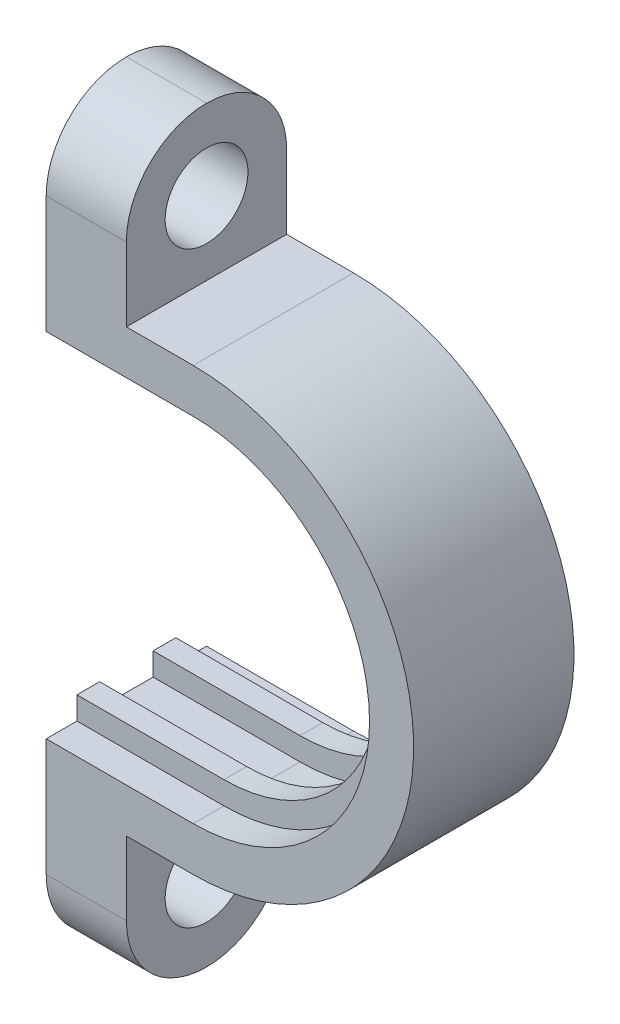
SolidWorks part; units mm, degrees
ref_plane "前视基准面" through (0, 0, 0) normal (0, 0, 1) x (1, 0, 0)
ref_plane "上视基准面" through (0, 0, 0) normal (0, 1, 0) x (1, 0, 0)
ref_plane "右视基准面" through (0, 0, 0) normal (1, 0, 0) x (0, 0, -1)
other "Configuration Table"
sketch "草图1" plane through (0, 0, 0) normal (0, 0, 1) x (1, 0, 0)
  line L14 (-5.5, 14) -> (-5.5, 5.75)
  line L15 (-5.5, -5.75) -> (-5.5, -14)
  line L16 (-2.5, 14) -> (-2.5, 8.25)
  line L17 (-2.5, -8.25) -> (-2.5, -14)
  line L18 (-2.5, 14) -> (-2.5, 8.3853) construction
  line L19 (-2.5, 14) -> (-5.5, 14)
  line L21 (-2.5, -14) -> (-5.5, -14)
  line L22 (-5.5, -1.6771) -> (-5.5, -8.3853) construction
  line L25 (-2.5, -8.3853) -> (-2.5, -8.3853) construction
  line L26 (-2.5, 8.25) -> (0, 8.25)
  line L27 (-2.5, -8.25) -> (0, -8.25)
  line L28 (0, 0) -> (5.75, 0) construction
  line L29 (0, 5.75) -> (-5.5, 5.75)
  line L30 (0, -5.75) -> (-5.5, -5.75)
  line L31 (-5.5, 14) -> (-5.5, 1.6771) construction
  arc A6 (0, 5.75) -> (0, -5.75) centre (0, 0) cw
  arc A8 (-2.5, 8.3853) -> (-2.5, -8.3853) centre (0, 0) cw construction
  arc A9 (-5.5, 1.6771) -> (-5.5, -1.6771) centre (0, 0) cw construction
  arc A10 (0, -8.25) -> (0, 8.25) centre (0, 0) ccw
  point P21 (-2.5, 8.242)
  point P22 (0, 8.25)
  dimension "D2" = 5.75
  dimension "D3" = 28
  dimension "D1" = 3
  dimension "D5" = 2.5
  dimension "D6" = 5.5
  dimension "D7" = 5.75
extrude "凸台-拉伸1" add sketch "草图1" along normal blind 6
sketch "草图2" plane through (-2.5, 0, 0) normal (1, 0, 0) x (0, 0, -1)
  line L0 (-6, -14) -> (0, -14) construction
  line L1 (-3, 0) -> (0, 0) construction
  line L3 (-3, 14) -> (-3, -14) construction
  line L7 (-6, 14) -> (0, 14) construction
  circle A0 centre (-3, -11) radius 1.55
  circle A1 centre (-3, -11) radius 3 construction
  circle A2 centre (-3, 11) radius 1.55
  point P18 (-3, 14)
  dimension "D1" = 3.1
  dimension "D2" = 6
  dimension "D4" = 3
extrude "切除-拉伸1" cut sketch "草图2" against normal blind 6
fillet "圆角2" radius 3 4 edges at (-4, -14, 0) (-4, -14, 6) (-4, 14, 0) (-4, 14, 6)
sketch "草图3" plane through (-5.5, 0, 0) normal (-1, 0, 0) x (0, 0, 1)
  line L0 (0, 0) -> (6, 0) construction
  line L1 (6, -5.75) -> (6, 5.75) construction
  line L2 (6, 5.75) -> (0, 5.75) construction
  line L3 (-0.85, 5.75) -> (1.15, 5.75)
  line L4 (-0.85, 5.75) -> (-0.85, 6.6)
  line L5 (-0.85, 6.6) -> (1.15, 6.6)
  line L6 (1.15, 5.75) -> (1.15, 6.6)
  line L7 (2, 5.75) -> (4, 5.75)
  line L8 (2, 5.75) -> (2, 6.6)
  line L9 (2, 6.6) -> (4, 6.6)
  line L10 (4, 5.75) -> (4, 6.6)
  line L11 (4.85, -6.6) -> (6.85, -6.6)
  line L12 (4.85, 5.75) -> (6.85, 5.75)
  line L13 (4.85, 5.75) -> (4.85, 6.6)
  line L14 (4.85, 6.6) -> (6.85, 6.6)
  line L15 (6.85, 5.75) -> (6.85, 6.6)
  line L16 (6.85, -5.75) -> (6.85, -6.6)
  line L17 (4.85, -5.75) -> (6.85, -5.75)
  line L18 (4.85, -5.75) -> (4.85, -6.6)
  line L19 (2, -6.6) -> (4, -6.6)
  line L20 (4, -5.75) -> (4, -6.6)
  line L21 (2, -5.75) -> (4, -5.75)
  line L22 (2, -5.75) -> (2, -6.6)
  line L23 (-0.85, -6.6) -> (1.15, -6.6)
  line L24 (1.15, -5.75) -> (1.15, -6.6)
  line L25 (-0.85, -5.75) -> (1.15, -5.75)
  line L26 (-0.85, -5.75) -> (-0.85, -6.6)
  line L28 (6, 5.75) -> (0, 5.75) construction
  line L29 (3, 0) -> (3, 14) construction
  dimension "D1" = 0.85
  dimension "D2" = 0.85
  dimension "D3" = 2
  dimension "D4" = 13.2
extrude "切除-拉伸2" cut sketch "草图3" against normal up to vertex (5.5 mm away) up to point (0, 5.75, 0)
sketch "草图4" plane through (0, 0, 0) normal (-1, 0, 0) x (0, 0, 1)
  line L0 (6, 6.6) -> (4.85, 6.6) construction
  line L1 (4.85, 6.6) -> (4.85, 5.75) construction
  line L2 (4.85, 5.75) -> (6, 5.75) construction
  line L3 (6, 5.75) -> (6, 6.6) construction
  line L4 (2, 6.6) -> (2, 5.75) construction
  line L5 (2, 5.75) -> (4, 5.75) construction
  line L6 (4, 5.75) -> (4, 6.6) construction
  line L7 (4, 6.6) -> (2, 6.6) construction
  line L8 (0, 6.6) -> (0, 5.75) construction
  line L9 (0, 5.75) -> (1.15, 5.75) construction
  line L10 (1.15, 5.75) -> (1.15, 6.6) construction
  line L11 (1.15, 6.6) -> (0, 6.6) construction
  line L12 (6, 6.6) -> (4.85, 6.6)
  line L13 (4.85, 6.6) -> (4.85, 5.75)
  line L14 (4.85, 5.75) -> (6, 5.75)
  line L15 (6, 5.75) -> (6, 6.6)
  line L16 (2, 6.6) -> (2, 5.75)
  line L17 (2, 5.75) -> (4, 5.75)
  line L18 (4, 5.75) -> (4, 6.6)
  line L19 (4, 6.6) -> (2, 6.6)
  line L20 (0, 6.6) -> (0, 5.75)
  line L21 (0, 5.75) -> (1.15, 5.75)
  line L22 (1.15, 5.75) -> (1.15, 6.6)
  line L23 (1.15, 6.6) -> (0, 6.6)
  line L24 (0, 0) -> (6, 0) construction
  line L25 (6, -5.75) -> (6, 5.75) construction
revolve "切除-旋转1" cut sketch "草图4" angle 360 about L24
